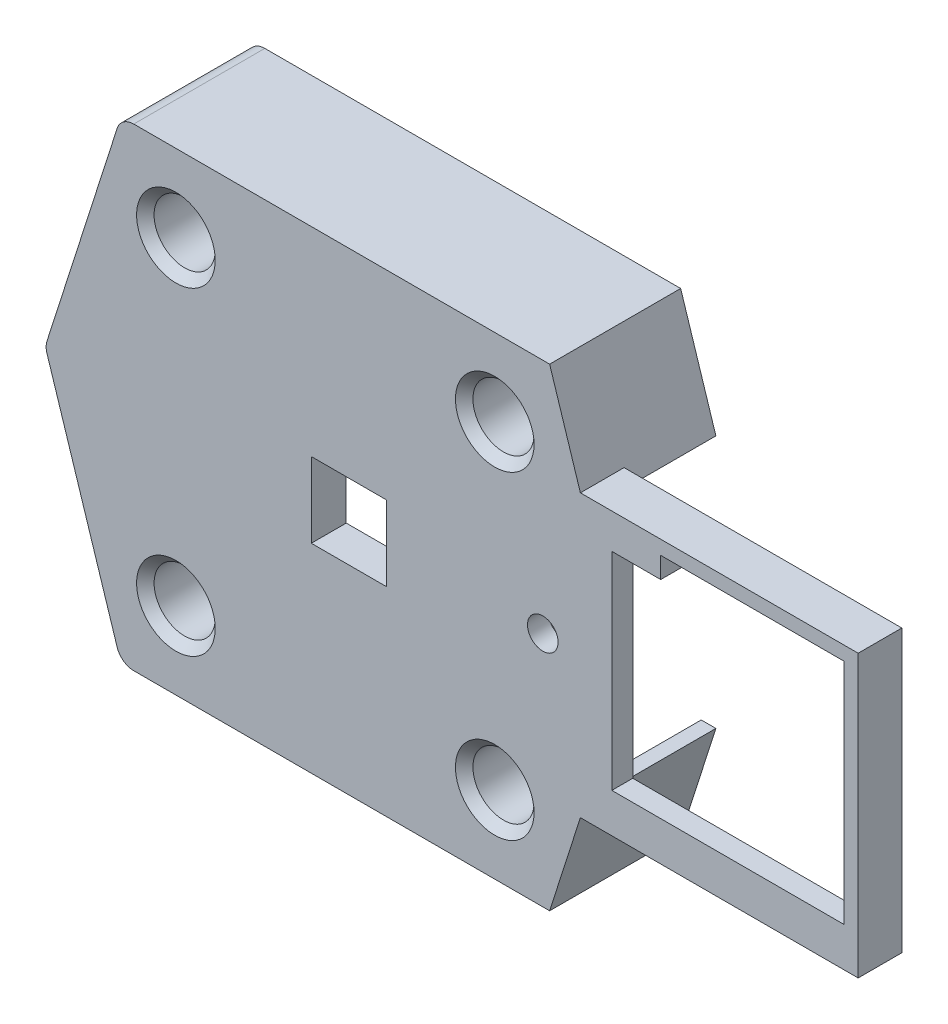
SolidWorks part; units mm, degrees
ref_plane "Front Plane" through (0, 0, 0) normal (0, 0, 1) x (1, 0, 0)
ref_plane "Top Plane" through (0, 0, 0) normal (0, 1, 0) x (1, 0, 0)
ref_plane "Right Plane" through (0, 0, 0) normal (1, 0, 0) x (0, 0, -1)
sketch "Sketch2" plane through (0, 0, 12) normal (0, 0, 1) x (1, 0, 0)
  line L10 (-24.5329, 27.1) -> (-33.2049, 0)
  line L11 (-33.2049, 0) -> (-24.5329, -27.1)
  line L12 (-24.5329, -27.1) -> (24.5329, -27.1)
  line L13 (24.5329, -27.1) -> (33.2049, 0)
  line L14 (33.2049, 0) -> (24.5329, 27.1)
  line L15 (24.5329, 27.1) -> (-24.5329, 27.1)
  line L16 (-23.365, 25.5) -> (-31.525, 0)
  line L17 (-31.525, 0) -> (-23.365, -25.5)
  line L18 (-23.365, -25.5) -> (23.365, -25.5)
  line L19 (23.365, -25.5) -> (31.525, 0)
  line L20 (31.525, 0) -> (23.365, 25.5)
  line L21 (23.365, 25.5) -> (-23.365, 25.5)
  line L22 (-23.365, 25.5) -> (-31.525, 0)
  line L23 (-31.525, 0) -> (-23.365, -25.5)
  line L24 (-23.365, -25.5) -> (23.365, -25.5)
  line L25 (23.365, -25.5) -> (31.525, 0)
  line L26 (31.525, 0) -> (23.365, 25.5)
  line L27 (23.365, 25.5) -> (-23.365, 25.5)
  dimension "D1" = 0.5
  dimension "D2" = 1.6
extrude "Boss-Extrude1" add sketch "Sketch2" along normal blind 10 and the other way blind 5
sketch "Sketch3" plane through (0, 0, 22) normal (0, 0, 1) x (1, 0, 0)
  line L0 (29.75, 16.1) -> (59.85, 16.1)
  line L1 (59.85, 16.1) -> (59.85, -16.1)
  line L2 (59.85, -16.1) -> (29.75, -16.1)
  line L3 (29.75, 16.1) -> (28.0529, 16.1)
  line L4 (28.0529, 16.1) -> (28.5649, 14.5)
  line L5 (29.75, -16.1) -> (28.0529, -16.1)
  line L6 (28.0529, -16.1) -> (28.5649, -14.5)
  line L12 (29.75, 14.5) -> (28.5649, 14.5)
  line L13 (33.2049, 0) -> (24.5329, 27.1) construction
  line L14 (29.75, -14.5) -> (28.5649, -14.5)
  line L15 (58.25, -14.5) -> (29.75, -14.5)
  line L16 (58.25, 14.5) -> (58.25, -14.5)
  line L17 (29.75, 14.5) -> (58.25, 14.5)
  line L18 (58.25, -14.5) -> (29.75, -14.5)
  line L19 (58.25, 14.5) -> (58.25, -14.5)
  line L20 (29.75, 14.5) -> (58.25, 14.5)
  line L21 (24.5329, -27.1) -> (33.2049, 0) construction
  dimension "D1" = 0.5
  dimension "D2" = 1.6
extrude "Boss-Extrude2" add sketch "Sketch3" against normal blind 5
sketch "Sketch4" plane through (0, 0, 7) normal (0, 0, -1) x (-1, 0, 0)
  line L0 (-28.5649, 14.5) -> (-26.885, 14.5)
  line L1 (-31.525, 0) -> (-23.365, 25.5) construction
  line L2 (-28.5649, -14.5) -> (-26.885, -14.5)
  line L3 (-23.365, -25.5) -> (-31.525, 0) construction
  line L6 (24.5329, 27.1) -> (-24.5329, 27.1)
  line L7 (-24.5329, 27.1) -> (-33.2049, 0)
  line L8 (-33.2049, 0) -> (-24.5329, -27.1)
  line L9 (-24.5329, -27.1) -> (24.5329, -27.1)
  line L10 (24.5329, -27.1) -> (33.2049, 0)
  line L11 (33.2049, 0) -> (24.5329, 27.1)
  line L12 (24.5329, 27.1) -> (-24.5329, 27.1)
  line L13 (-24.5329, 27.1) -> (-33.2049, 0)
  line L14 (-33.2049, 0) -> (-24.5329, -27.1)
  line L15 (-24.5329, -27.1) -> (24.5329, -27.1)
  line L16 (24.5329, -27.1) -> (33.2049, 0)
  line L17 (33.2049, 0) -> (24.5329, 27.1)
  line M7 (-31.525, 0) -> (-23.365, 25.5)
  line M12 (-23.365, -25.5) -> (-31.525, 0)
  line M14 (-24.5329, 27.1) -> (-33.2049, 0)
  line M15 (-33.2049, 0) -> (-24.5329, -27.1)
  dimension "D1" = 0
extrude "Cut-Extrude1" cut sketch "Sketch4" against normal through all contours L2 L0 M15 M12 M7 M14 region at (27.7249, 14.2032, 7)
sketch "Sketch5" plane through (0, 0, 22) normal (0, 0, 1) x (1, 0, 0)
  line L0 (-2.25, 3.8) -> (-2.25, -3.8) construction
  line L1 (-2.25, -3.8) -> (29.75, -3.8) construction
  line L2 (29.75, -3.8) -> (29.75, -14) construction
  line L3 (29.75, -14) -> (57.75, -14) construction
  line L4 (57.75, -14) -> (57.75, 14) construction
  line L5 (57.75, 14) -> (29.75, 14) construction
  line L6 (29.75, 14) -> (29.75, 3.8) construction
  line L7 (29.75, 3.8) -> (-2.25, 3.8) construction
  line L8 (24.5329, -27.1) -> (28.0529, -16.1) construction
  line L9 (28.0529, -16.1) -> (59.85, -16.1) construction
  line L10 (59.85, -16.1) -> (59.85, 16.1) construction
  line L11 (59.85, 16.1) -> (28.0529, 16.1) construction
  line L12 (28.0529, 16.1) -> (24.5329, 27.1) construction
  line L13 (24.5329, 27.1) -> (-24.5329, 27.1) construction
  line L14 (-24.5329, 27.1) -> (-33.2049, 0) construction
  line L15 (-33.2049, 0) -> (-24.5329, -27.1) construction
  line L16 (-24.5329, -27.1) -> (24.5329, -27.1) construction
  line L17 (-2.25, 3.8) -> (-2.25, -3.8)
  line L18 (-2.25, -3.8) -> (29.75, -3.8)
  line L19 (29.75, -3.8) -> (29.75, -14)
  line L20 (29.75, -14) -> (57.75, -14)
  line L21 (57.75, -14) -> (57.75, 14)
  line L22 (57.75, 14) -> (29.75, 14)
  line L23 (29.75, 14) -> (29.75, 3.8)
  line L24 (29.75, 3.8) -> (-2.25, 3.8)
  line L25 (24.5329, -27.1) -> (28.0529, -16.1)
  line L26 (28.0529, -16.1) -> (59.85, -16.1)
  line L27 (59.85, -16.1) -> (59.85, 16.1)
  line L28 (59.85, 16.1) -> (28.0529, 16.1)
  line L29 (28.0529, 16.1) -> (24.5329, 27.1)
  line L30 (24.5329, 27.1) -> (-24.5329, 27.1)
  line L31 (-24.5329, 27.1) -> (-33.2049, 0)
  line L32 (-33.2049, 0) -> (-24.5329, -27.1)
  line L33 (-24.5329, -27.1) -> (24.5329, -27.1)
  line L34 (29.25, 14) -> (29.25, 4.3)
  line L35 (29.25, 4.3) -> (-2.75, 4.3)
  line L36 (-2.75, 4.3) -> (-2.75, -4.3)
  line L37 (-2.75, -4.3) -> (29.25, -4.3)
  line L38 (29.25, -4.3) -> (29.25, -14)
  line L39 (29.25, 14) -> (29.25, 14.5)
  line L40 (26.885, 14.5) -> (58.25, 14.5) construction
  line L41 (29.25, -14) -> (29.25, -14.5)
  line L42 (58.25, -14.5) -> (26.885, -14.5) construction
  line L43 (27.65, 14) -> (27.65, 14.5)
  line L44 (27.65, 14) -> (27.65, 5.9)
  line L45 (27.65, 5.9) -> (-4.35, 5.9)
  line L46 (-4.35, 5.9) -> (-4.35, -5.9)
  line L47 (-4.35, -5.9) -> (27.65, -5.9)
  line L48 (27.65, -5.9) -> (27.65, -14)
  line L49 (27.65, -14) -> (27.65, -14.5)
  circle A0 centre (18.25, -18.25) radius 3.5 construction
  circle A1 centre (-18.25, -18.25) radius 3.5 construction
  circle A2 centre (-18.25, 18.25) radius 3.5 construction
  circle A3 centre (18.25, 18.25) radius 3.5 construction
  circle A4 centre (18.25, -18.25) radius 3.5
  circle A5 centre (-18.25, -18.25) radius 3.5
  circle A6 centre (-18.25, 18.25) radius 3.5
  circle A7 centre (18.25, 18.25) radius 3.5
  line M28 (26.885, 14.5) -> (58.25, 14.5)
  line M30 (58.25, -14.5) -> (26.885, -14.5)
  dimension "D1" = 0.5
  dimension "D2" = 1.6
extrude "Boss-Extrude3" add sketch "Sketch5" against normal blind 4 contours L48 L49 L41 L38 L37 L36 L35 L34 L39 L43 L44 L45 L46 L47 M30 M28 region at (28.8062, 9.15, 22)
sketch "Sketch7" plane through (0, 0, 22) normal (0, 0, 1) x (1, 0, 0)
  line L5 (37.25, 14.5) -> (37.25, 12.1)
  line L6 (29.25, 14.5) -> (58.25, 14.5) construction
  line L7 (37.25, 12.1) -> (31.65, 12.1)
  line L8 (31.65, 12.1) -> (31.65, -11.6)
  line L9 (31.65, -11.6) -> (58.25, -11.6)
  line L10 (58.25, 14.5) -> (58.25, -14.5) construction
  line L11 (5.85, 4.3) -> (5.85, -4.3)
  line L12 (29.25, 4.3) -> (-2.75, 4.3) construction
  line L13 (-2.75, -4.3) -> (29.25, -4.3) construction
  line L14 (29.25, 14.5) -> (29.25, 4.3) construction
  line L15 (-2.75, 4.3) -> (-2.75, -4.3) construction
  line L16 (29.75, -14) -> (57.75, -14) construction
  circle A0 centre (23.75, 0) radius 1.75 construction
  circle A1 centre (23.75, 0) radius 1.75
  line M29 (58.25, -14.5) -> (29.25, -14.5)
  line M30 (29.25, -14.5) -> (29.25, -4.3)
  line M31 (29.25, -4.3) -> (-2.75, -4.3)
  line M33 (-2.75, 4.3) -> (29.25, 4.3)
  line M34 (29.25, 4.3) -> (29.25, 14.5)
  line M35 (29.25, 14.5) -> (58.25, 14.5)
  line M36 (58.25, 14.5) -> (58.25, -14.5)
  dimension "D1" = 8.6
  dimension "D2" = 2.4
  dimension "D3" = 2.4
  dimension "D4" = 2.4
  dimension "D5" = 8
extrude "Boss-Extrude4" add sketch "Sketch7" against normal blind 2.4 contours L11 L9 L8 L7 L5 A1 M33 M31 M30 M29 M36 M35 M34 region at (26.5863, -2.3534, 22)
sketch "Sketch8" plane through (0, 0, 22) normal (0, 0, 1) x (1, 0, 0)
  circle A0 centre (-18.25, -18.25) radius 3.5 construction
  circle A1 centre (18.25, -18.25) radius 3.5 construction
  circle A2 centre (18.25, 18.25) radius 3.5 construction
  circle A3 centre (-18.25, 18.25) radius 3.5 construction
  circle A4 centre (-18.25, -18.25) radius 3.5
  circle A5 centre (18.25, -18.25) radius 3.5
  circle A6 centre (18.25, 18.25) radius 3.5
  circle A7 centre (-18.25, 18.25) radius 3.5
  line M11 (27.65, -5.9) -> (27.65, -14.5)
  line M12 (27.65, -14.5) -> (26.885, -14.5)
  line M13 (26.885, -14.5) -> (23.365, -25.5)
  line M14 (23.365, -25.5) -> (-23.365, -25.5)
  line M15 (-23.365, -25.5) -> (-31.525, 0)
  line M16 (-31.525, 0) -> (-23.365, 25.5)
  line M17 (-23.365, 25.5) -> (23.365, 25.5)
  line M18 (23.365, 25.5) -> (26.885, 14.5)
  line M19 (26.885, 14.5) -> (27.65, 14.5)
  line M20 (27.65, 14.5) -> (27.65, 5.9)
  line M21 (27.65, 5.9) -> (-4.35, 5.9)
  line M22 (-4.35, 5.9) -> (-4.35, -5.9)
  line M23 (-4.35, -5.9) -> (27.65, -5.9)
extrude "Boss-Extrude5" add sketch "Sketch8" against normal blind 1 contours A7 A6 A5 A4 M11 M23 M22 M21 M20 M19 M18 M17 M16 M15 M14 M13 M12 region at (26.8688, -10.2, 22)
sketch "Sketch9" plane through (0, 0, 21) normal (0, 0, -1) x (-1, 0, 0)
  circle A0 centre (-18.25, -18.25) radius 3.5 construction
  circle A1 centre (18.25, -18.25) radius 3.5 construction
  circle A2 centre (18.25, 18.25) radius 3.5 construction
  circle A3 centre (-18.25, 18.25) radius 3.5 construction
  circle A4 centre (-18.25, -18.25) radius 3.5
  circle A5 centre (18.25, -18.25) radius 3.5
  circle A6 centre (18.25, 18.25) radius 3.5
  circle A7 centre (-18.25, 18.25) radius 3.5
  circle A8 centre (-18.25, 18.25) radius 5.1
  circle A9 centre (18.25, 18.25) radius 5.1
  circle A10 centre (18.25, -18.25) radius 5.1
  circle A11 centre (-18.25, -18.25) radius 5.1
  dimension "D1" = 1.6
extrude "Boss-Extrude6" add sketch "Sketch9" along normal blind 9
chamfer "Chamfer1" distance 1 angle 45 4 edges at (-14.75, -18.25, 22) (21.75, -18.25, 22) (21.75, 18.25, 22) (-14.75, 18.25, 22)
fillet "Fillet1" radius 2 3 edges at (-24.5329, 27.1, 14.5) (-33.2049, 0, 14.5) (-24.5329, -27.1, 14.5)
